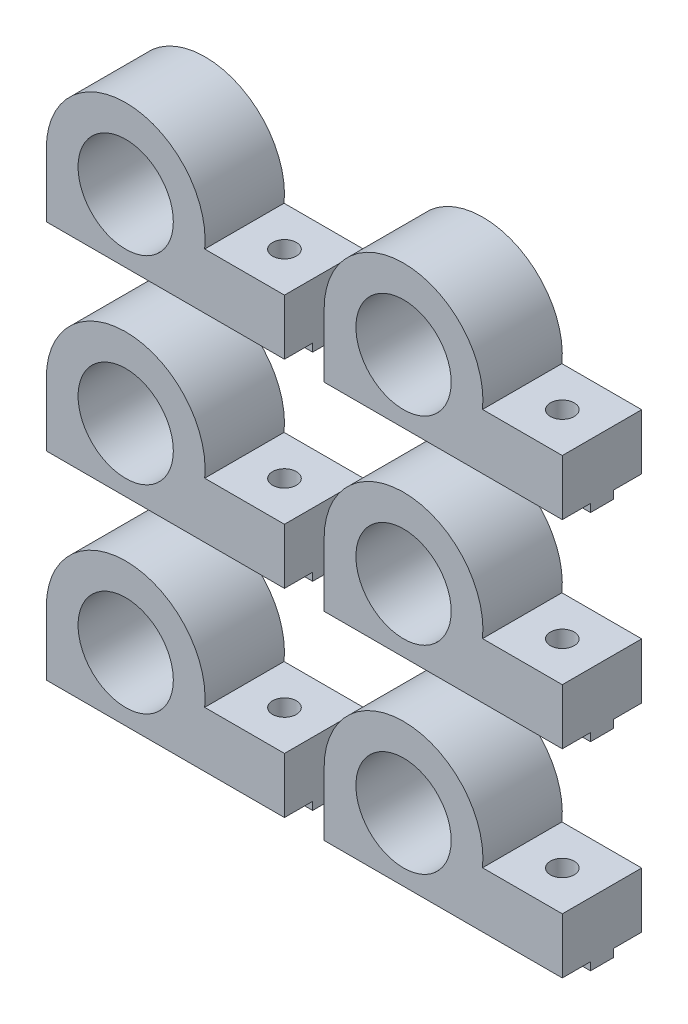
SolidWorks part; units mm, degrees
ref_plane "Front Plane" through (0, 0, 0) normal (0, 0, 1) x (1, 0, 0)
ref_plane "Top Plane" through (0, 0, 0) normal (0, 1, 0) x (1, 0, 0)
ref_plane "Right Plane" through (0, 0, 0) normal (1, 0, 0) x (0, 0, -1)
sketch "Sketch1" plane through (0, 0, 0) normal (0, 0, 1) x (1, 0, 0)
  line L0 (-10, 0) -> (-10, -8)
  line L1 (20, -8) -> (20, -1)
  line L3 (-10, -8) -> (20, -8)
  line L4 (20, -1) -> (9.9499, -1)
  arc A0 (-10, 0) -> (9.9499, -1) centre (0, 0) cw
  circle A1 centre (0, 0) radius 6
  dimension "D1" = 12
  dimension "D2" = 10
  dimension "D3" = 8
  dimension "D4" = 7
  dimension "D5" = 30
extrude "Main" add sketch "Sketch1" along normal blind 10
sketch "Sketch3" plane through (0, -8, 0) normal (0, -1, 0) x (-1, 0, 0)
  line L0 (10, -10) -> (10, 0) construction
  line L1 (10, -6.45) -> (-20, -6.45)
  line L2 (10, -6.45) -> (10, -3.55)
  line L3 (10, -3.55) -> (-20, -3.55)
  line L4 (-20, -6.45) -> (-20, -3.55)
  line L5 (-20, -10) -> (-20, 0) construction
  line L6 (10, 0) -> (-20, 0) construction
  dimension "D1" = 2.9
  dimension "D2" = 3.55
extrude "MakerBeamRectangularGuide" add sketch "Sketch3" along normal blind 1
sketch "Sketch4" plane through (0, -1, 0) normal (0, 1, 0) x (1, 0, 0)
  line L0 (20, -10) -> (9.9499, -10) construction
  line L1 (20, -10) -> (20, 0) construction
  circle A0 centre (15, -5) radius 1.5
  dimension "D1" = 3
  dimension "D2" = 5
  dimension "D3" = 5
extrude "MakerBeamFixHole" cut sketch "Sketch4" against normal through all
pattern_linear "LPattern1" count 3 spacing 25 along (0, -1, 0) count 2 spacing 35 along (-1, 0, 0) of bodies 103
